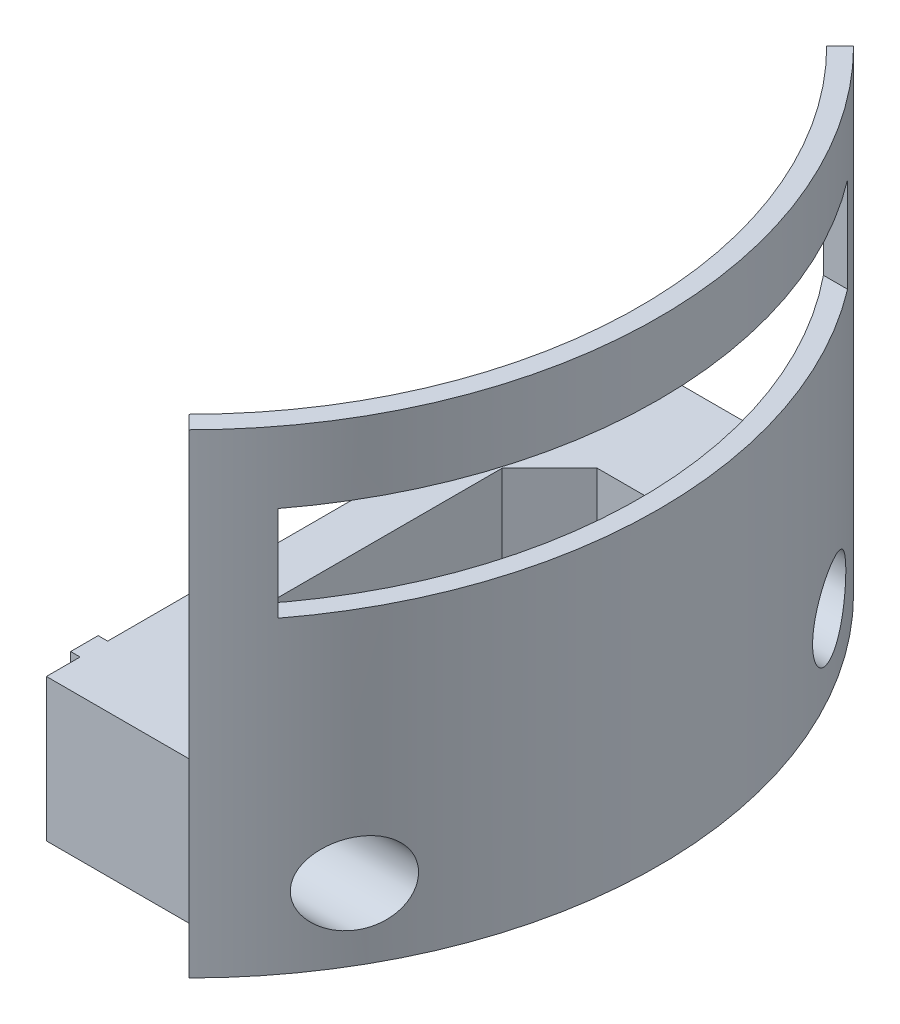
SolidWorks part; units mm, degrees
ref_plane "Front Plane" through (0, 0, 0) normal (0, 0, 1) x (1, 0, 0)
ref_plane "Top Plane" through (0, 0, 0) normal (0, 1, 0) x (1, 0, 0)
ref_plane "Right Plane" through (0, 0, 0) normal (1, 0, 0) x (0, 0, -1)
ref_axis "Axis1" through (0, -0.2847, 0) along (0, 1, 0)
ref_plane "SupportPlain" through (0, 10, 0) normal (0, 1, 0) x (1, 0, 0)
sketch "Sketch1" plane through (0, 0, 0) normal (0, 0, 1) x (1, 0, 0)
  line L0 (49.5, 0) -> (49.5, 50)
  line L5 (49.5, 50) -> (47.5, 50)
  line L6 (47.5, 50) -> (47.5, 0)
  line L7 (47.5, 0) -> (49.5, 0)
  point P9 (48.5, 0)
  dimension "D1" = 50
  dimension "D2" = 2
  dimension "D3" = 49.5
revolve "Main" add sketch "Sketch1" angle 90 mid plane about axis through (0, -0.2847, 0) along (0, 1, 0)
sketch "Sketch2" plane through (0, 0, 0) normal (0, -1, 0) x (-1, 0, 0)
  line L0 (-43.9574, -18) -> (-20, -18)
  line L1 (-36.8273, -30) -> (-15, -30)
  line L2 (-33.5876, -33.5876) -> (-33.5876, 33.5876) construction
  line L9 (-43.9574, 18) -> (-20, 18)
  line L10 (-15, -30) -> (-15, 30)
  line L11 (-15, 30) -> (-36.8273, 30)
  line L13 (-20, 18) -> (-20, -18)
  arc A0 (-43.9574, 18) -> (-36.8273, 30) centre (0, 0) cw
  circle A1 centre (0, 0) radius 50 construction
  arc A2 (-36.8273, -30) -> (-43.9574, -18) centre (0, 0) cw
  circle A3 centre (0, 0) radius 47.5 construction
  point P4 (0, 0)
  point P7 (0, 0)
  point P26 (-15, 0)
  dimension "D7" = 12
  dimension "D4" = 100
  dimension "D1" = 12
  dimension "D2" = 15
  dimension "D3" = 5
  dimension "D5" = 60
extrude "Support" add sketch "Sketch2" against normal blind 15
sketch "Sketch6" plane through (0, 0, 0) normal (0, 1, 0) x (1, 0, 0)
  line L0 (15, -30) -> (15, 30) construction
  line L1 (14, -23.55) -> (15, -23.55)
  line L2 (14, -23.55) -> (14, -26.45)
  line L3 (14, -26.45) -> (15, -26.45)
  line L4 (15, -23.55) -> (15, -26.45)
  line L6 (14, 26.45) -> (15, 26.45)
  line L7 (14, 26.45) -> (14, 23.55)
  line L8 (14, 23.55) -> (15, 23.55)
  line L9 (15, 26.45) -> (15, 23.55)
  line L11 (15, -30) -> (15, 30) construction
  point P10 (15, -30)
  point P13 (15, 30)
  dimension "D1" = 3.55
  dimension "D2" = 2.9
  dimension "D3" = 1
  dimension "D4" = 3.55
extrude "Fix" add sketch "Sketch6" along normal up to surface (15 mm away) up to face at (29.057, 15, 0)
sketch "Sketch9" plane through (20, 0, 0) normal (1, 0, 0) x (0, 0, -1)
  line L0 (26.45, 0) -> (23.55, 0) construction
  line L1 (30, 15) -> (30, 0) construction
  line L2 (-30, 15) -> (-30, 0) construction
  line L3 (30, 15) -> (30, 0) construction
  line L4 (-30, 32) -> (30, 32)
  line L5 (-30, 32) -> (-30, 24)
  line L6 (-30, 24) -> (30, 24)
  line L7 (30, 32) -> (30, 24)
  line L8 (-30, 15) -> (-30, 0) construction
  line L9 (-23.55, 0) -> (23.55, 0) construction
  circle A0 centre (25, 7.5) radius 1.6
  circle A1 centre (-25, 7.5) radius 1.6
  dimension "D1" = 3.2
  dimension "D2" = 3.2
  dimension "D3" = 7.5
  dimension "D4" = 5
  dimension "D5" = 5
  dimension "D6" = 8
  dimension "D7" = 24
extrude "Holes" cut sketch "Sketch9" against normal through all
sketch "Sketch10" plane through (20, 0, 0) normal (1, 0, 0) x (0, 0, -1)
  circle A0 centre (25, 7.5) radius 4.25
  circle A1 centre (-25, 7.5) radius 4.25
  arc A2 (23.55, 6.8236) -> (26.45, 6.8236) centre (25, 7.5) ccw construction
  arc A3 (-26.45, 6.8236) -> (-23.55, 6.8236) centre (-25, 7.5) ccw construction
  dimension "D1" = 8.5
extrude "BigHoles" cut sketch "Sketch10" along normal through all
sketch "Sketch11" plane through (0, 15, 0) normal (0, 1, 0) x (1, 0, 0)
  line L0 (20, 18) -> (25, 18)
  line L2 (25, 18) -> (20, 13)
  line L3 (20, 18) -> (20, -18) construction
  line L4 (20, 13) -> (20, 18)
  line L5 (20, -18) -> (20, -13)
  line L6 (20, -13) -> (25, -18)
  line L7 (20, -18) -> (43.9574, -18) construction
  line L8 (25, -18) -> (20, -18)
  line L9 (41.1113, 18) -> (46.1113, 18)
  line L10 (46.1113, 18) -> (46.1113, 13)
  line L11 (46.1113, 13) -> (41.1113, 18)
  line L12 (41.1113, -18) -> (46.1113, -18)
  line L13 (46.1113, -18) -> (46.1113, -11.4018)
  line L14 (46.1113, -11.4018) -> (41.1113, -18)
  line L15 (43.9574, 18) -> (20, 18) construction
  arc A0 (35.0018, -35.0018) -> (35.0018, 35.0018) centre (0, 0) ccw construction
  arc A1 (33.5876, -33.5876) -> (33.5876, 33.5876) centre (0, 0) ccw construction
  point P3 (20, 18)
  point P4 (45.2797, 17.657)
  point P22 (0, 0)
  point P27 (20, 20)
  point P28 (40.2797, 18)
  dimension "D1" = 5
  dimension "D2" = 5
  dimension "D3" = 5
extrude "Reinforcement" add sketch "Sketch11" against normal blind 10
sketch "Sketch12" plane through (15, 0, 0) normal (-1, 0, 0) x (0, 0, 1)
  line L0 (-30, 15) -> (-30, 0) construction
  line L1 (-30, 32.5) -> (30, 32.5)
  line L2 (-30, 32.5) -> (-30, 42.5)
  line L3 (-30, 42.5) -> (30, 42.5)
  line L4 (30, 32.5) -> (30, 42.5)
  line L5 (30, 15) -> (30, 0) construction
  line L6 (23.55, 0) -> (-23.55, 0) construction
  line L7 (35.0018, 50) -> (-35.0018, 50) construction
  dimension "D1" = 32.5
  dimension "D2" = 10
  dimension "D3" = 7.5
extrude "SensorWindow" cut sketch "Sketch12" against normal through all
